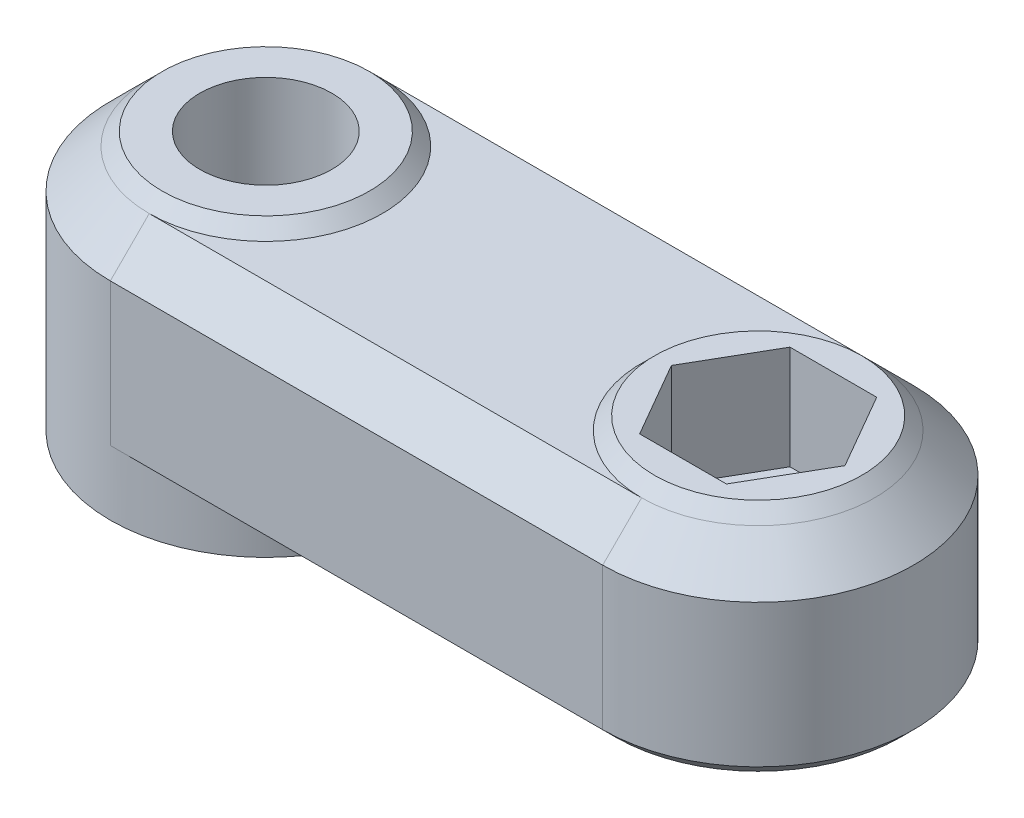
SolidWorks part; units mm, degrees
ref_plane "Front Plane" through (0, 0, 0) normal (0, 0, 1) x (1, 0, 0)
ref_plane "Top Plane" through (0, 0, 0) normal (0, 1, 0) x (1, 0, 0)
ref_plane "Right Plane" through (0, 0, 0) normal (1, 0, 0) x (0, 0, -1)
sketch "Sketch1" plane through (0, 0, 0) normal (0, 1, 0) x (1, 0, 0)
  line L0 (0, 0) -> (19, 0) construction
  line L1 (0, 6) -> (19, 6)
  line L2 (0, -6) -> (19, -6)
  arc A0 (0, 6) -> (0, -6) centre (0, 0) ccw
  arc A1 (19, -6) -> (19, 6) centre (19, 0) ccw
  point P3 (9.5, 0)
  dimension "D1" = 19
  dimension "D2" = 12
extrude "Boss-Extrude1" add sketch "Sketch1" along normal blind 10
sketch "Sketch2" plane through (0, 0, 0) normal (0, 0, 1) x (1, 0, 0)
  line L0 (0, 0) -> (0, 13.6635) construction
  line L1 (0, 10) -> (-2.55, 10)
  line L2 (0, 10) -> (-6, 10) construction
  line L3 (-2.55, 10) -> (-2.55, 5)
  line L4 (-2.55, 5) -> (-2.1, 5)
  line L5 (-2.1, 5) -> (-2.1, 2)
  line L6 (-2.1, 2) -> (-2.55, 2)
  line L7 (-2.55, 2) -> (-2.55, 0)
  line L8 (-2.55, 0) -> (0, 0)
  line L9 (0, 0) -> (0, 10)
  dimension "D1" = 5.1
  dimension "D2" = 4.2
  dimension "D3" = 5
  dimension "D4" = 3
revolve "Cut-Revolve1" cut sketch "Sketch2" angle 360 about L0
sketch "Sketch3" plane through (0, 0, 0) normal (0, 0, 1) x (1, 0, 0)
  line L0 (19, 0) -> (19, 13.4014) construction
  line L1 (19, 10) -> (16.5, 10)
  line L2 (0, 10) -> (19, 10) construction
  line L3 (16.5, 10) -> (16.5, 6)
  line L4 (16.5, 6) -> (16.925, 6)
  line L5 (16.925, 6) -> (16.925, 0)
  line L6 (0, 0) -> (19, 0) construction
  line L7 (16.925, 0) -> (19, 0)
  line L8 (19, 0) -> (19, 10)
  dimension "D1" = 4.15
  dimension "D2" = 5
  dimension "D3" = 6
revolve "Cut-Revolve2" cut sketch "Sketch3" angle 360 about L0
chamfer "Chamfer1" distance 2 angle 45 4 edges at (9.5, 10, 6) (25, 10, 0) (-6, 10, 0) (9.5, 10, -6)
sketch "Sketch4" plane through (0, 0, 0) normal (0, -1, 0) x (1, 0, 0)
  line L0 (0, 6) -> (19, 6) construction
  line L1 (2.1073, 3.65) -> (-2.1073, 3.65)
  line L2 (-2.1073, 3.65) -> (-4.2147, 0)
  line L3 (-4.2147, 0) -> (-2.1073, -3.65)
  line L4 (-2.1073, -3.65) -> (2.1073, -3.65)
  line L5 (2.1073, -3.65) -> (4.2147, 0)
  line L6 (4.2147, 0) -> (2.1073, 3.65)
  circle A0 centre (0, 0) radius 3.65 construction
  dimension "D1" = 7.3
extrude "Cut-Extrude1" cut sketch "Sketch4" against normal blind 5
sketch "Sketch5" plane through (0, 0, 0) normal (0, -1, 0) x (1, 0, 0)
  circle A0 centre (0, 0) radius 6
  circle A1 centre (0, 0) radius 34.2024
  arc A2 (19, -6) -> (19, 6) centre (19, 0) ccw construction
extrude "Cut-Extrude2" cut sketch "Sketch5" against normal blind 2
sketch "Sketch6" plane through (0, 10, 0) normal (0, 1, 0) x (1, 0, 0)
  line L0 (19, -6) -> (0, -6) construction
  line L1 (20.6743, -2.9) -> (22.3486, 0)
  line L2 (22.3486, 0) -> (20.6743, 2.9)
  line L3 (20.6743, 2.9) -> (17.3257, 2.9)
  line L4 (17.3257, 2.9) -> (15.6514, 0)
  line L5 (15.6514, 0) -> (17.3257, -2.9)
  line L6 (17.3257, -2.9) -> (20.6743, -2.9)
  circle A0 centre (19, 0) radius 2.9 construction
  dimension "D1" = 5.8
extrude "Cut-Extrude3" cut sketch "Sketch6" against normal blind 4
chamfer "Chamfer2" distance 0.5 angle 45 3 edges at (9.5, 2, 6) (25, 2, 0) (9.5, 2, -6)
sketch "Sketch7" plane through (0, 10, 0) normal (0, 1, 0) x (1, 0, 0)
  line L1 (29.9124, 9.576) -> (-11.0103, 9.576)
  line L2 (29.9124, 9.576) -> (29.9124, -12.5783)
  line L3 (29.9124, -12.5783) -> (-11.0103, -12.5783)
  line L4 (-11.0103, 9.576) -> (-11.0103, -12.5783)
  circle A0 centre (19, 0) radius 4
  circle A1 centre (0, 0) radius 4
  arc A2 (19, -4) -> (19, 4) centre (19, 0) ccw construction
  arc A3 (0, 4) -> (0, -4) centre (0, 0) ccw construction
extrude "Cut-Extrude4" cut sketch "Sketch7" against normal blind 0.5
chamfer "Chamfer3" distance 0.5 angle 45 2 edges at (0, 9.5, 4) (19, 9.5, 4)
